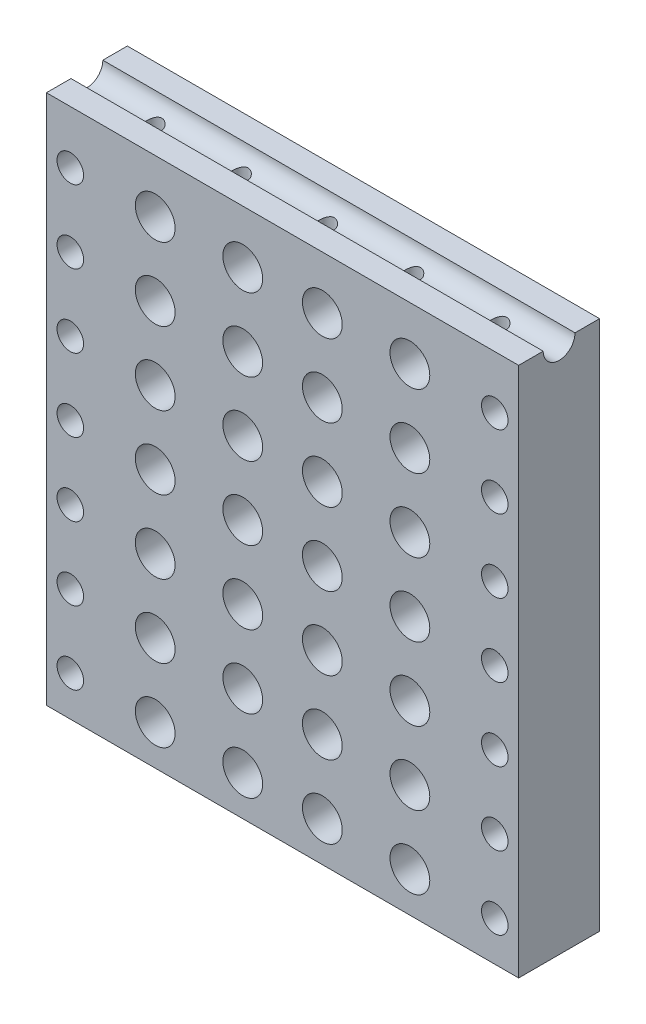
SolidWorks part; units mm, degrees
note: The reader was unsure of these and kept them because the rebuilt part matched: shared geometry of "Sketch4<2>", "Sketch4<3>".
ref_plane "Front Plane" through (0, 0, 0) normal (0, 0, 1) x (1, 0, 0)
ref_plane "Top Plane" through (0, 0, 0) normal (0, 1, 0) x (1, 0, 0)
ref_plane "Right Plane" through (0, 0, 0) normal (1, 0, 0) x (0, 0, -1)
sketch "Sketch1" plane through (0, 0, 0) normal (0, 0, 1) x (1, 0, 0)
  line L5 (-178, 200) -> (178, 200)
  line L6 (-178, 200) -> (-178, -200)
  line L8 (-178, -200) -> (178, -200)
  line L10 (178, 200) -> (178, -200)
  line L12 (-178, 200) -> (178, -200) construction
  line L13 (-178, -200) -> (178, 200) construction
  point P0 (0, 0)
  dimension "D1" = 356
  dimension "D2" = 400
extrude "Boss-Extrude1" add sketch "Sketch1" along normal mid plane 61
sketch "Sketch4" plane through (0, 200, 0) normal (0, 1, 0) x (1, 0, 0)
  line L0 (-178, -30.5) -> (-178, 30.5) construction
  line L1 (178, 30.5) -> (-178, 30.5) construction
  circle A0 centre (-128, 0.5) radius 10
  circle A9 centre (-128, 0.5) radius 6
  circle A20 centre (-63, 0.5) radius 6
  circle A21 centre (-63, 0.5) radius 10
  circle A22 centre (2, 0.5) radius 6
  circle A23 centre (2, 0.5) radius 10
  circle A24 centre (67, 0.5) radius 6
  circle A25 centre (67, 0.5) radius 10
  circle A26 centre (132, 0.5) radius 6
  circle A27 centre (132, 0.5) radius 10
  dimension "D2" = 12
  dimension "D3" = 20
  dimension "D5" = 50
  dimension "D8" = 30
  dimension "D1" = 115
extrude "Boss-Extrude2" add sketch "Sketch4" against normal through all
sketch "Sketch6" plane through (178, 0, 0) normal (1, 0, 0) x (0, 0, -1)
  line L0 (-30.5, 200) -> (30.5, 200) construction
  line L1 (-12, 200) -> (12, 200)
  arc A0 (-12, 200) -> (12, 200) centre (0, 200) ccw
  dimension "D1" = 24
extrude "Cut-Extrude1" cut sketch "Sketch6" against normal through all
extrude "Cut-Extrude2" cut sketch "Sketch4<2>" against normal through all
sketch "Sketch4<2>" plane through (0, 200, 0) normal (0, 1, 0) x (1, 0, 0) same geometry as "Sketch4"
extrude "Cut-Extrude3" cut sketch "Sketch4<3>" against normal through all contours A9 | A20 | A22 | A24 | A26
sketch "Sketch4<3>" plane through (0, 200, 0) normal (0, 1, 0) x (1, 0, 0) same geometry as "Sketch4"
sketch "Sketch8" plane through (0, 0, 30.5) normal (0, 0, 1) x (1, 0, 0)
  line L0 (-30, 221.4017) -> (-30, -224.698) construction
  line L1 (0, 0) -> (0, 247.7721) construction
  line L2 (30, 221.4017) -> (30, -224.698) construction
  line L3 (178, 200) -> (-178, 200) construction
  line L4 (160, 221.4017) -> (160, -224.698) construction
  line L5 (30, 221.4017) -> (30, -224.698) construction
  line L6 (-63, 200) -> (-63, -240.1994) construction
  line L7 (-53, 200) -> (-73, 200) construction
  line L8 (-96, 221.4017) -> (-96, -224.698) construction
  line L9 (96, 221.4017) -> (96, -224.698) construction
  line L10 (-128, 200) -> (-128, -240.1994) construction
  line L11 (-122, 200) -> (-134, 200) construction
  line L12 (-160, 221.4017) -> (-160, -224.698) construction
  line L13 (178, -200) -> (178, 200) construction
  circle A0 centre (-30, 160) radius 15
  circle A1 centre (-30, 105) radius 15
  circle A2 centre (-30, 50) radius 15
  circle A3 centre (-30, -5) radius 15
  circle A4 centre (-30, -60) radius 15
  circle A5 centre (-30, -115) radius 15
  circle A6 centre (-30, -170) radius 15
  circle A7 centre (30, -170) radius 15
  circle A8 centre (30, -115) radius 15
  circle A9 centre (30, -60) radius 15
  circle A10 centre (30, -5) radius 15
  circle A11 centre (30, 50) radius 15
  circle A12 centre (30, 105) radius 15
  circle A13 centre (30, 160) radius 15
  circle A14 centre (-96, -170) radius 15
  circle A15 centre (-96, -115) radius 15
  circle A16 centre (-96, -60) radius 15
  circle A17 centre (-96, -5) radius 15
  circle A18 centre (-96, 50) radius 15
  circle A19 centre (-96, 105) radius 15
  circle A20 centre (-96, 160) radius 15
  circle A21 centre (96, 160) radius 15
  circle A22 centre (96, 105) radius 15
  circle A23 centre (96, 50) radius 15
  circle A24 centre (96, -5) radius 15
  circle A25 centre (96, -60) radius 15
  circle A26 centre (96, -115) radius 15
  circle A27 centre (96, -170) radius 15
  circle A28 centre (-160, 160) radius 10
  circle A35 centre (-160, 105) radius 10
  circle A36 centre (-160, 50) radius 10
  circle A37 centre (-160, -5) radius 10
  circle A38 centre (-160, -60) radius 10
  circle A39 centre (-160, -115) radius 10
  circle A40 centre (-160, -170) radius 10
  circle A41 centre (160, -170) radius 10
  circle A42 centre (160, -115) radius 10
  circle A43 centre (160, -60) radius 10
  circle A44 centre (160, -5) radius 10
  circle A45 centre (160, 50) radius 10
  circle A46 centre (160, 105) radius 10
  circle A47 centre (160, 160) radius 10
  dimension "D2" = 30
  dimension "D8" = 20
  dimension "D1" = 30
  dimension "D3" = 40
  dimension "D4" = 21.4017
  dimension "D5" = 95
  dimension "D6" = 424.698
  dimension "D10" = 55
  dimension "D7" = 7
  dimension "D9" = 7
extrude "Cut-Extrude4" cut sketch "Sketch8" against normal through all
